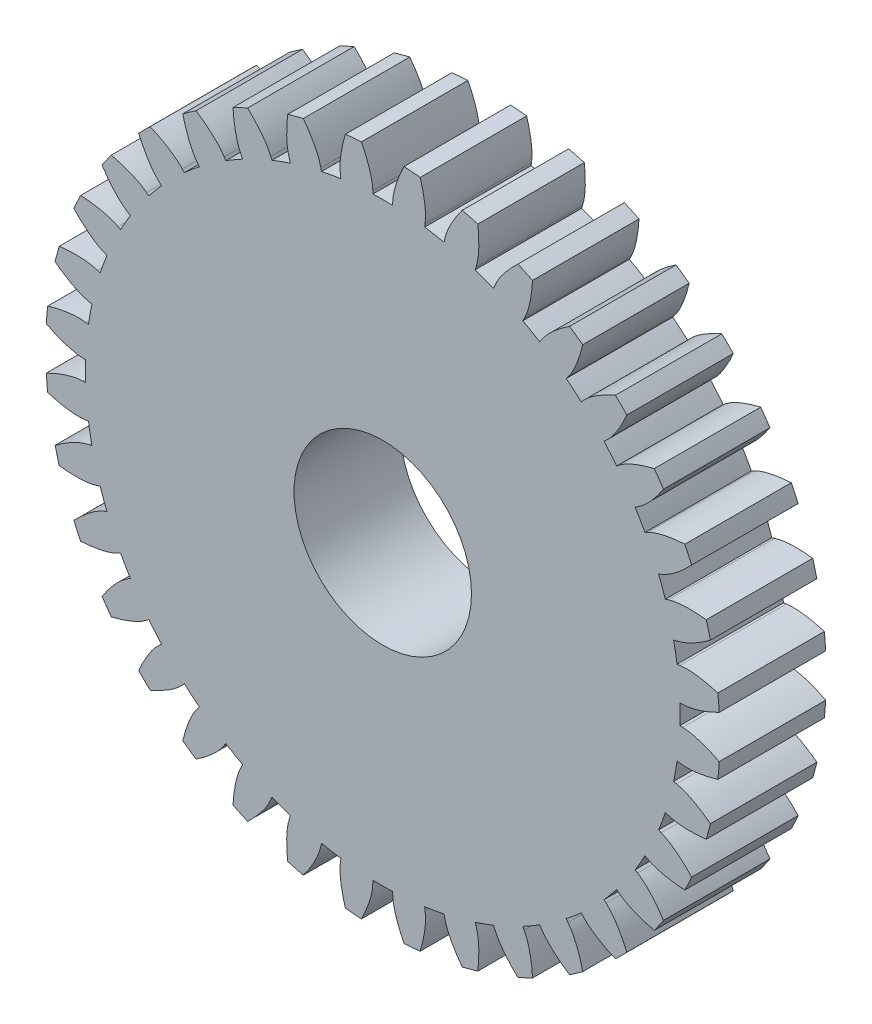
SolidWorks part; units mm, degrees
ref_plane "前视基准面" through (0, 0, 0) normal (0, 0, 1) x (1, 0, 0)
ref_plane "上视基准面" through (0, 0, 0) normal (0, 1, 0) x (1, 0, 0)
ref_plane "右视基准面" through (0, 0, 0) normal (1, 0, 0) x (0, 0, -1)
other "Configuration Table"
sketch "草图1" plane through (0, 0, 0) normal (0, 0, 1) x (1, 0, 0)
  line L0 (0, 0) -> (3.6, 0) construction
  line L1 (0, 0) -> (3.5966, 0.157) construction
  line L2 (0, 0) -> (3.381, 0.112)
  line L3 (3.5966, 0.157) -> (3.5966, -0.157) construction
  line L4 (0, 0) -> (3.381, -0.112)
  circle A0 centre (0, 0) radius 3.8
  circle A1 centre (0, 0) radius 3.6 construction
  circle A2 centre (0, 0) radius 3.35
  circle A3 centre (0, 0) radius 3.3829 construction
  circle A4 centre (0, 0) radius 1
  spline S0 degree 4 poles (3.381, 0.112) (3.4068, 0.1129) (3.4786, 0.1206) (3.6122, 0.1567) (3.8186, 0.2443) (4.0657, 0.3983) (4.3517, 0.6388) (4.641, 0.9681) (4.9035, 1.3715) (5.1787, 1.9586) (5.3541, 2.5843) (5.441, 3.2533) (5.4347, 4.056) (5.3255, 4.8527) (5.0648, 5.7502) (4.6247, 6.6904) (4.0541, 7.5571) (3.3722, 8.3386) (2.5962, 9.0265) (1.743, 9.6151) (0.8269, 10.1008) (-0.0158, 10.434) (-0.7616, 10.6539) (-1.3282, 10.7795) (-1.7135, 10.8471) (-2.0273, 10.8924) (-2.2969, 10.9228) (-2.5087, 10.9435) (-2.7499, 10.9593) (-2.9945, 10.9718) (-3.2391, 10.9781) (-3.6692, 10.9794) (-4.0193, 10.9593) (-4.3829, 10.9359) (-4.5587, 10.9128) (-4.6763, 10.901) knots 0 0 0 0 0 0.005604 0.015718 0.02996 0.048734 0.068727 0.096889 0.125051 0.153212 0.209535 0.237696 0.271429 0.327752 0.384075 0.440398 0.496721 0.553044 0.609367 0.66569 0.722013 0.778336 0.806497 0.834659 0.84874 0.86282 0.876901 0.890982 0.900036 0.909091 0.931818 0.954545 0.977273 1 1 1 1 1 construction
  spline S1 degree 4 poles (3.381, 0.112) (3.4068, 0.1129) (3.4786, 0.1206) (3.6122, 0.1567) (3.8186, 0.2443) (4.0657, 0.3983) (4.3517, 0.6388) (4.641, 0.9681) (4.9035, 1.3715) (5.1787, 1.9586) (5.3541, 2.5843) (5.441, 3.2533) (5.4347, 4.056) (5.3255, 4.8527) (5.0648, 5.7502) (4.6247, 6.6904) (4.0541, 7.5571) (3.3722, 8.3386) (2.5962, 9.0265) (1.743, 9.6151) (0.8269, 10.1008) (-0.0158, 10.434) (-0.7616, 10.6539) (-1.3282, 10.7795) (-1.7135, 10.8471) (-2.0273, 10.8924) (-2.2969, 10.9228) (-2.5087, 10.9435) (-2.7499, 10.9593) (-2.8933, 10.9666) (-2.9691, 10.9697) (-3.0068, 10.971) knots 0 0 0 0 0 0.005604 0.015718 0.02996 0.048734 0.068727 0.096889 0.125051 0.153212 0.209535 0.237696 0.271429 0.327752 0.384075 0.440398 0.496721 0.553044 0.609367 0.66569 0.722013 0.778336 0.806497 0.834659 0.84874 0.86282 0.876901 0.890982 0.900036 0.909091 0.909091 0.909091 0.909091 0.909091
  spline S2 degree 4 poles (3.381, -0.112) (3.4068, -0.1129) (3.4786, -0.1206) (3.6122, -0.1567) (3.8186, -0.2443) (4.0657, -0.3983) (4.3517, -0.6388) (4.641, -0.9681) (4.9035, -1.3715) (5.1787, -1.9586) (5.3541, -2.5843) (5.441, -3.2533) (5.4347, -4.056) (5.3255, -4.8527) (5.0648, -5.7502) (4.6247, -6.6904) (4.0541, -7.5571) (3.3722, -8.3386) (2.5962, -9.0265) (1.743, -9.6151) (0.8269, -10.1008) (-0.0158, -10.434) (-0.7616, -10.6539) (-1.3282, -10.7795) (-1.7135, -10.8471) (-2.0273, -10.8924) (-2.2969, -10.9228) (-2.5087, -10.9435) (-2.7499, -10.9593) (-2.9945, -10.9718) (-3.2391, -10.9781) (-3.6692, -10.9794) (-4.0193, -10.9593) (-4.3829, -10.9359) (-4.5587, -10.9128) (-4.6763, -10.901) knots 0 0 0 0 0 0.005604 0.015718 0.02996 0.048734 0.068727 0.096889 0.125051 0.153212 0.209535 0.237696 0.271429 0.327752 0.384075 0.440398 0.496721 0.553044 0.609367 0.66569 0.722013 0.778336 0.806497 0.834659 0.84874 0.86282 0.876901 0.890982 0.900036 0.909091 0.931818 0.954545 0.977273 1 1 1 1 1 construction
  spline S3 degree 4 poles (3.381, -0.112) (3.4068, -0.1129) (3.4786, -0.1206) (3.6122, -0.1567) (3.8186, -0.2443) (4.0657, -0.3983) (4.3517, -0.6388) (4.641, -0.9681) (4.9035, -1.3715) (5.1787, -1.9586) (5.3541, -2.5843) (5.441, -3.2533) (5.4347, -4.056) (5.3255, -4.8527) (5.0648, -5.7502) (4.6247, -6.6904) (4.0541, -7.5571) (3.3722, -8.3386) (2.5962, -9.0265) (1.743, -9.6151) (0.8269, -10.1008) (-0.0158, -10.434) (-0.7616, -10.6539) (-1.3282, -10.7795) (-1.7135, -10.8471) (-2.0273, -10.8924) (-2.2969, -10.9228) (-2.5087, -10.9435) (-2.7499, -10.9593) (-2.8933, -10.9666) (-2.9691, -10.9697) (-3.0068, -10.971) knots 0 0 0 0 0 0.005604 0.015718 0.02996 0.048734 0.068727 0.096889 0.125051 0.153212 0.209535 0.237696 0.271429 0.327752 0.384075 0.440398 0.496721 0.553044 0.609367 0.66569 0.722013 0.778336 0.806497 0.834659 0.84874 0.86282 0.876901 0.890982 0.900036 0.909091 0.909091 0.909091 0.909091 0.909091
  point P15 (3.5966, 0)
  dimension "齿顶圆直径" = 7.6
  dimension "分度圆直径" = 7.2
  dimension "齿根圆直径" = 6.7
  dimension "基圆直径" = 6.7658
  dimension "内孔直径" = 2
  dimension "渐近线镜像线夹角" = 2.5
extrude "凸台-拉伸1" add sketch "草图1" along normal blind 1.2 contours A0 | A4
extrude "切除-拉伸1" cut sketch "草图1<3>" along normal through all contours A2 S3 A0 S1 region at (3.6055, 0, 0)
sketch "草图1<3>" plane through (0, 0, 0) normal (0, 0, 1) x (1, 0, 0) same geometry as "草图1"
pattern_circular "阵列(圆周)1" count 36 every 10 about axis through (0, 0, 1.2) along (0, 0, 1) of "切除-拉伸1"
equation "\"m\"= 0.2'模数"
equation "\"z\"= 36'齿数"
equation "\"a\"= 20度'压力角"
equation "\"d\"= \"m\" * \"z\"'分度圆直径"
equation "\"da\"= ( \"z\" + 2 ) * \"m\"'齿顶圆直径"
equation "\"df\"= ( \"z\" - 2.5 ) * \"m\"'齿根圆直径"
equation "\"s\"= 0.5 * PI * \"m\"'分度圆齿厚"
equation "\"r\"= 0.38 * \"m\"'齿根圆角"
equation "\"B\"= 0.3 * \"d\"'齿厚"
equation "\"db\"= \"m\" * \"z\" * cos ( \"a\" )'基圆直径"
equation "\"rb\"= \"db\" / 2'基圆半径"
equation "\"齿顶圆直径@草图1\"= \"da\""
equation "\"分度圆直径@草图1\"= \"d\""
equation "\"齿根圆直径@草图1\"= \"df\""
equation "\"基圆直径@草图1\"= \"db\""
equation "\"渐近线镜像线夹角@草图1\"= 360 / 4 / \"z\""
equation "\"h\"= 1.2'齿轮厚度"
equation "\"ir\"= 2'内孔直径"
equation "\"内孔直径@草图1\"= \"ir\""
equation "\"齿轮厚@凸台-拉伸1\"= \"h\""
equation "\"齿轮夹角@阵列(圆周)1\"= 360 / \"z\""
equation "\"齿数@阵列(圆周)1\"= \"z\""
